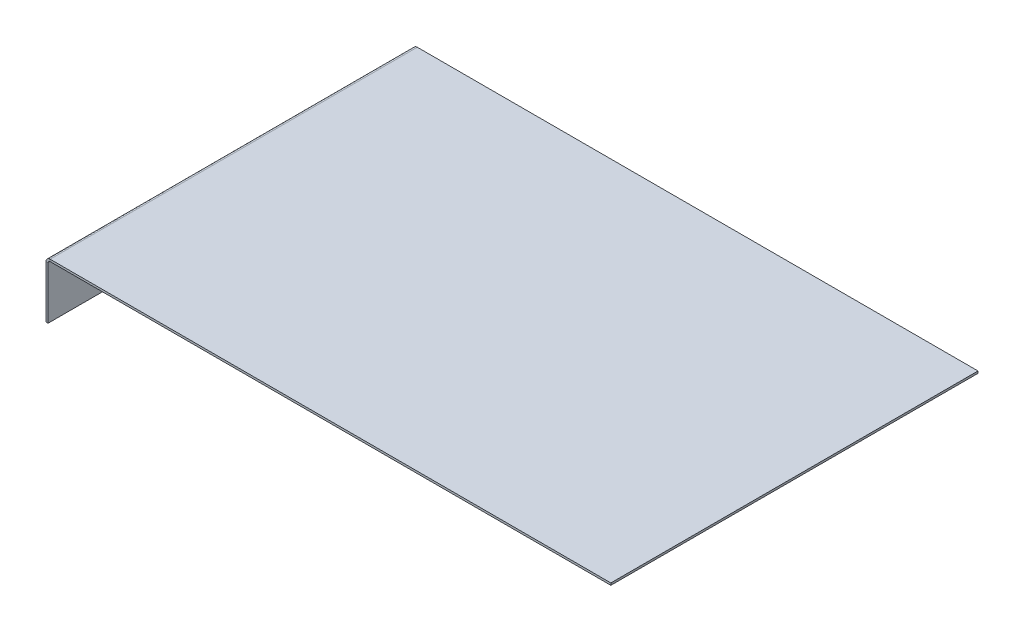
SolidWorks part; units mm, degrees
note: The reader was unsure of these and kept them because the rebuilt part matched: flange length of "Edge-Flange1".
ref_plane "Front Plane" through (0, 0, 0) normal (0, 0, 1) x (1, 0, 0)
ref_plane "Top Plane" through (0, 0, 0) normal (0, 1, 0) x (1, 0, 0)
ref_plane "Right Plane" through (0, 0, 0) normal (1, 0, 0) x (0, 0, -1)
sketch "Sketch1" plane through (0, 0, 0) normal (0, 1, 0) x (1, 0, 0)
  line L1 (-100, -65) -> (100, -65)
  line L2 (-100, -65) -> (-100, 65)
  line L3 (-100, 65) -> (100, 65)
  line L4 (100, -65) -> (100, 65)
  line L5 (-100, -65) -> (100, 65) construction
  line L6 (-100, 65) -> (100, -65) construction
  point P0 (0, 0)
  dimension "D1" = 200
  dimension "D2" = 130
base flange "Base-Flange1" sketch "Sketch1" thickness 0.7366 reverse thickness direction no parameters "D1"=0.7366
edge flange "Edge-Flange1" sketch "Sketch10" flange angle 90 flange length 20 flange position material inside bend radius 0.7366 thickness 0.7366 relief rectangular parameters "D6"=10
sketch "Sketch10" plane through (-100, -0.7366, 0) normal (-1, 0, 0) x (0, 0, -1)
  line L0 (65, 0) -> (-65, 0) construction
  line L1 (65, 0) -> (-65, 0)
  line L2 (-65, 0) -> (-65, 19.2634)
  line L3 (-65, 19.2634) -> (65, 19.2634)
  line L4 (65, 19.2634) -> (65, 0)
bend "EdgeBend1" bend radius 0.7366 bend angle 90 parameters "D5"=1
sketch "Bend-Lines1" plane through (0, 0, 0) normal (0, 1, 0) x (1, 0, 0)
sketch "Bounding-Box1" plane through (0, 0, 0) normal (0, 1, 0) x (1, 0, 0)
sheet metal parameters "Sheet-Metal2" thickness 0.7366 parameters "D1"=0.7366
flat pattern "Flat-Pattern2" [suppressed]
sketch "Bend-Lines2" plane through (0, 0, 0) normal (0, 1, 0) x (1, 0, 0)
sketch "Bounding-Box2" [suppressed] plane through (0, 0, 0) normal (0, 1, 0) x (1, 0, 0)
sheet metal parameters "Sheet-Metal3" thickness 0.7366 parameters "D1"=0.7366
flat pattern "Flat-Pattern2" [suppressed]
sketch "Bend-Lines2" plane through (0, 0, 0) normal (0, 1, 0) x (1, 0, 0)
sketch "Bounding-Box2" [suppressed] plane through (0, 0, 0) normal (0, 1, 0) x (1, 0, 0)
bend of the flat pattern "Flatten-<EdgeBend1>1"
